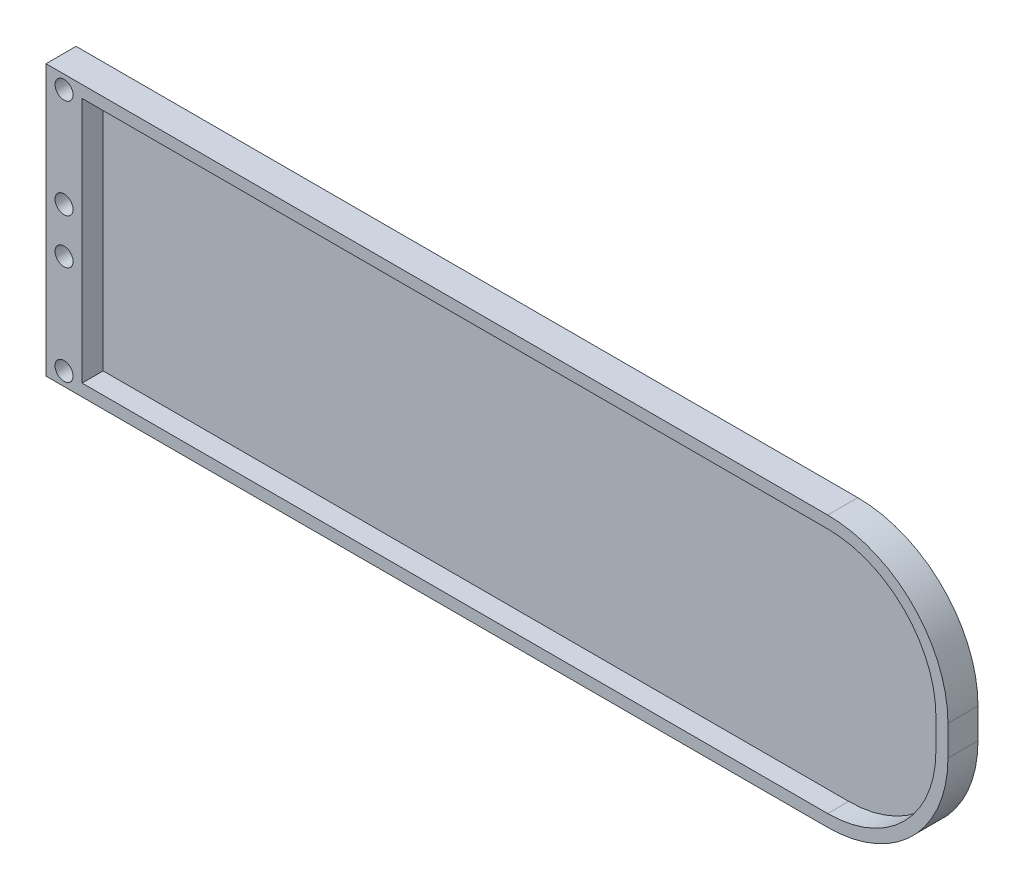
SolidWorks part; units mm, degrees
ref_plane "Front Plane" through (0, 0, 0) normal (0, 0, 1) x (1, 0, 0)
ref_plane "Top Plane" through (0, 0, 0) normal (0, 1, 0) x (1, 0, 0)
ref_plane "Right Plane" through (0, 0, 0) normal (1, 0, 0) x (0, 0, -1)
sketch "Sketch1" plane through (0, 0, 0) normal (0, 0, 1) x (1, 0, 0)
  line L0 (-150, 0) -> (0, 0) construction
  line L1 (110, -45) -> (-150, -45)
  line L2 (150, -5) -> (150, 5)
  line L3 (110, 45) -> (-150, 45)
  line L4 (-150, -45) -> (-150, 45)
  line L5 (150, -45) -> (-150, 45) construction
  line L6 (150, 45) -> (-150, -45) construction
  line L7 (-144, -7.5) -> (-144, 7.5) construction
  line L8 (-144, 7.5) -> (-144, 0) construction
  line L9 (-144, -40.5) -> (-144, 40.5) construction
  line L10 (-138, 45) -> (-138, -45)
  line L11 (110, 41) -> (-138, 41)
  line L13 (110, -41) -> (-138, -41)
  line L14 (146, -5) -> (146, 5)
  line L15 (110, 41) -> (-146, 41) construction
  line L16 (-146, -41) -> (-146, 41) construction
  line L17 (110, -41) -> (-146, -41) construction
  arc A0 (110, -45) -> (150, -5) centre (110, -5) ccw
  arc A1 (150, 5) -> (110, 45) centre (110, 5) ccw
  circle A2 centre (-144, 40.5) radius 3
  circle A3 centre (-144, 7.5) radius 3
  circle A4 centre (-144, -7.5) radius 3
  circle A5 centre (-144, -40.5) radius 3
  arc A6 (110, -41) -> (146, -5) centre (110, -5) ccw
  arc A7 (146, 5) -> (110, 41) centre (110, 5) ccw
  point P0 (0, 0)
  point P17 (-144, 0)
  point P21 (-144, 0)
  dimension "D2" = 6
  dimension "D6" = 40
  dimension "D1" = 300
  dimension "D3" = 15
  dimension "D4" = 81
  dimension "D5" = 90
  dimension "D7" = 6
  dimension "D8" = 12
  dimension "D9" = 4
extrude "Boss-Extrude1" add sketch "Sketch1" along normal blind 3 contours L2 A1 L3 L10 L1 A0 | L14 A7 L11 L10 L13 A6 region at (-14, -41.9827, 0) region at (0.722, 0, 0)
extrude "Boss-Extrude2" add sketch "Sketch1<3>" along normal blind 10 contours L10 L3 L4 L1 A5 A4 A3 A2 | A7 L14 A6 L13 L10 L1 A0 L2 A1 L3 L11 region at (-14, -41.9827, 0) region at (-144, 0, 0)
sketch "Sketch1<3>" plane through (0, 0, 0) normal (0, 0, 1) x (1, 0, 0) same geometry as "Sketch1"
